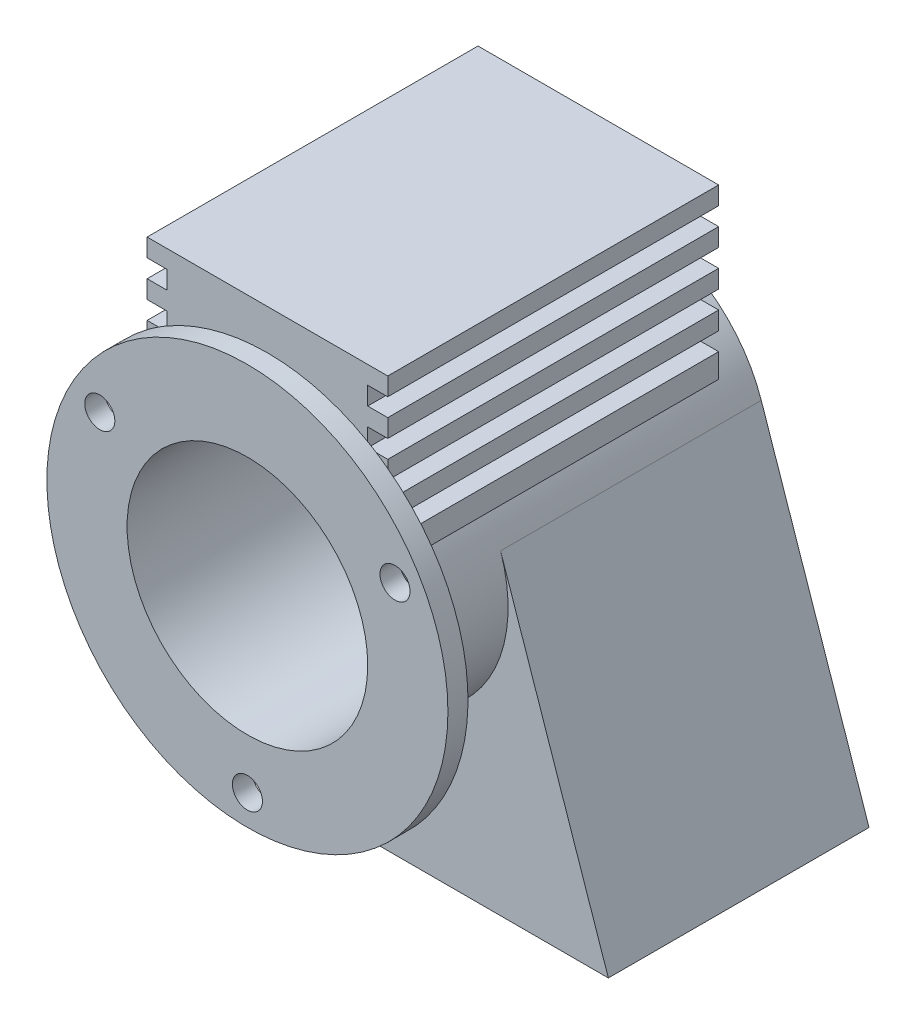
SolidWorks part; units mm, degrees
ref_plane "Front Plane" through (0, 0, 0) normal (0, 0, 1) x (1, 0, 0)
ref_plane "Top Plane" through (0, 0, 0) normal (0, 1, 0) x (1, 0, 0)
ref_plane "Right Plane" through (0, 0, 0) normal (1, 0, 0) x (0, 0, -1)
sketch "Sketch1" plane through (0, 0, 0) normal (0, 0, 1) x (1, 0, 0)
  line L0 (-6, -6.75) -> (6, -6.75)
  line L1 (-6, -6.75) -> (-3.3126, 1.1298)
  line L2 (6, -6.75) -> (3.3126, 1.1298)
  arc A0 (3.3126, 1.1298) -> (-3.3126, 1.1298) centre (0, 0) ccw
  point P6 (0, -6.75)
  dimension "D1" = 7
  dimension "D2" = 12
  dimension "D3" = 6.75
extrude "Boss-Extrude1" add sketch "Sketch1" along normal mid plane 6.5
sketch "Sketch2" plane through (0, 0, 3.25) normal (0, 0, 1) x (1, 0, 0)
  circle A0 centre (0, 0) radius 3.5
extrude "Boss-Extrude2" add sketch "Sketch2" along normal blind 2.5
sketch "Sketch3" plane through (0, 0, 5.75) normal (0, 0, 1) x (1, 0, 0)
  circle A0 centre (0, 0) radius 5
  dimension "D1" = 10
extrude "Boss-Extrude3" add sketch "Sketch3" along normal blind 0.5
sketch "Sketch5" plane through (0, 0, 5.75) normal (0, 0, -1) x (-1, 0, 0)
  line L0 (-3, -1.8028) -> (-3, -1.7725)
  line L1 (-3, 6) -> (3, 6)
  line L2 (-3, 6) -> (-3, 1.8028)
  line L3 (-3, -1.7725) -> (-3.018, -1.7725)
  line L4 (3, 6) -> (3, 1.8028)
  arc A2 (3, 1.8028) -> (-3, 1.8028) centre (0, 0) ccw
  point P1 (0, 6)
  circle M2 centre (0, 0) radius 3.5
  circle M3 centre (0, 0) radius 5
  dimension "D1" = 6
  dimension "D2" = 6
extrude "Boss-Extrude4" add sketch "Sketch5" along normal blind 8.25 contours L4 L2 M3 M2 | L4 L1 L2 M3 region at (0, 3.8001, 5.75) region at (0, 5.3081, 5.75)
sketch "Sketch6" plane through (0, 0, -2.5) normal (0, 0, -1) x (-1, 0, 0)
  line L1 (-3, 6) -> (-3, 1.8028) construction
  line L2 (-3, 6) -> (3, 6) construction
  line L3 (-3, 5.55) -> (-3, 5.1)
  line L4 (-3, 5.55) -> (-2.5, 5.55)
  line L5 (-2.5, 5.55) -> (-2.5, 5.1)
  line L6 (-2.5, 5.1) -> (-3, 5.1)
  dimension "D1" = 0.45
  dimension "D2" = 0.5
  dimension "D3" = 0.45
extrude "Cut-Extrude1" cut sketch "Sketch6" against normal blind 8.25
pattern_linear "LPattern1" count 4 spacing 0.9 along (0, -1, 0) of "Cut-Extrude1"
mirror "Mirror1" about plane through (0, 0, 0) normal (1, 0, 0) of "LPattern1"
sketch "Sketch7" plane through (0, 0, 6.25) normal (0, 0, 1) x (1, 0, 0)
  circle A0 centre (0, 0) radius 3
  circle A1 centre (0, -4.25) radius 0.375
  circle A2 centre (-3.6806, 2.125) radius 0.375
  circle A3 centre (3.6806, 2.125) radius 0.375
  circle A4 centre (0, 0) radius 0.75
  point P11 (0, 0)
  dimension "D1" = 6
  dimension "D2" = 0.75
  dimension "D5" = 1.5
  dimension "D3" = 4.25
  dimension "D4" = 3
extrude "Cut-Extrude2" cut sketch "Sketch7" against normal blind 9 contours A0
extrude "Cut-Extrude3" cut sketch "Sketch7<4>" against normal through all contours A4
sketch "Sketch7<4>" plane through (0, 0, 6.25) normal (0, 0, 1) x (1, 0, 0) same geometry as "Sketch7"
extrude "Cut-Extrude4" cut sketch "Sketch7<5>" against normal up to next contours A1 | A2 | A3 region at (0, -4.25, 6.25)
sketch "Sketch7<5>" plane through (0, 0, 6.25) normal (0, 0, 1) x (1, 0, 0) same geometry as "Sketch7"
